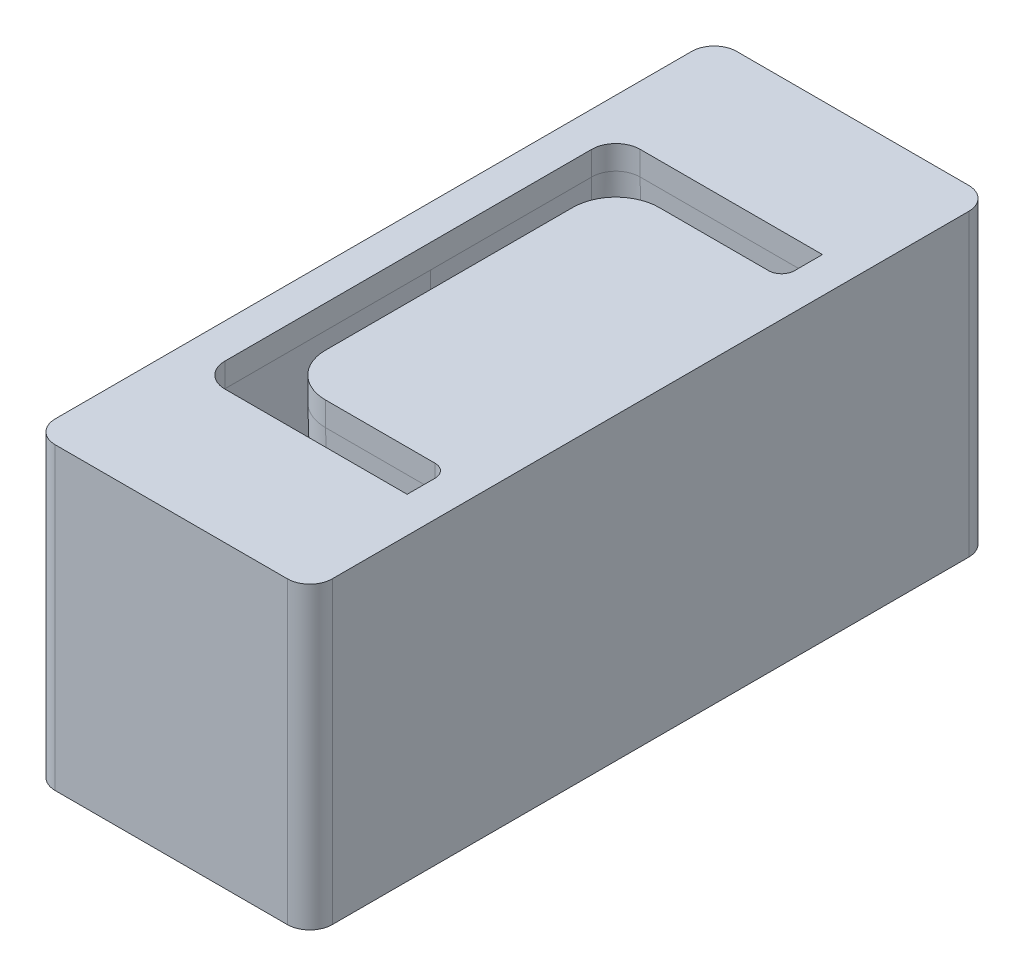
SolidWorks part; units mm, degrees
material "K110"
ref_plane "Front Plane" through (0, 0, 0) normal (0, 0, 1) x (1, 0, 0)
ref_plane "Top Plane" through (0, 0, 0) normal (0, 1, 0) x (1, 0, 0)
ref_plane "Right Plane" through (0, 0, 0) normal (1, 0, 0) x (0, 0, -1)
sketch "Sketch1" plane through (0, 0, 0) normal (0, 1, 0) x (1, 0, 0)
  line L1 (-8, -48.5) -> (29, -48.5)
  line L2 (-8, -48.5) -> (-8, 42.5)
  line L3 (-8, 42.5) -> (29, 42.5)
  line L4 (29, -48.5) -> (29, 42.5)
  line L5 (10.5, 42.5) -> (10.5, -48.5) construction
  line L6 (26, 42.5) -> (-5, 42.5) construction
  line L8 (-5, -48.5) -> (26, -48.5) construction
  line L9 (29, -3) -> (-8, -3) construction
  line L10 (29, -45.5) -> (29, 39.5) construction
  line L11 (-8, 39.5) -> (-8, -45.5) construction
  point P0 (0, 0)
extrude "Boss-Extrude1" add sketch "Sketch1" against normal blind 40
fillet "Fillet1" radius 3 4 edges at (-8, -20, -42.5) (29, -20, -42.5) (29, -20, 48.5) (-8, -20, 48.5)
sketch "Sketch2" plane through (0, 0, 0) normal (0, 1, 0) x (1, 0, 0)
  line L46 (24.23, 24.73) -> (-0.12, 24.73)
  line L47 (24.23, 21) -> (24.23, 24.73)
  line L48 (7.88, 19.27) -> (22.5, 19.27)
  line L49 (2.11, -19.5) -> (2.11, 13.5)
  line L60 (22.5, -25.27) -> (7.88, -25.27)
  line L61 (24.23, -30.73) -> (24.23, -27)
  line L62 (-0.12, -30.73) -> (24.23, -30.73)
  line L63 (-3.35, 21.5) -> (-3.35, -27.5)
  line L64 (24.23, 24.73) -> (-0.12, 24.73)
  line L65 (24.23, 21) -> (24.23, 24.73)
  line L66 (7.88, 19.27) -> (22.5, 19.27)
  line L67 (2.11, -19.5) -> (2.11, 13.5)
  line L68 (22.5, -25.27) -> (7.88, -25.27)
  line L69 (24.23, -30.73) -> (24.23, -27)
  line L70 (-0.12, -30.73) -> (24.23, -30.73)
  line L71 (-3.35, 21.5) -> (-3.35, -27.5)
  arc A36 (-0.12, 24.73) -> (-3.35, 21.5) centre (-0.12, 21.5) ccw
  arc A37 (22.5, 19.27) -> (24.23, 21) centre (22.5, 21) ccw
  arc A38 (7.88, 19.27) -> (2.11, 13.5) centre (7.88, 13.5) ccw
  arc A39 (2.11, -19.5) -> (7.88, -25.27) centre (7.88, -19.5) ccw
  arc A40 (24.23, -27) -> (22.5, -25.27) centre (22.5, -27) ccw
  arc A41 (-3.35, -27.5) -> (-0.12, -30.73) centre (-0.12, -27.5) ccw
  arc A42 (-0.12, 24.73) -> (-3.35, 21.5) centre (-0.12, 21.5) ccw
  arc A43 (22.5, 19.27) -> (24.23, 21) centre (22.5, 21) ccw
  arc A44 (7.88, 19.27) -> (2.11, 13.5) centre (7.88, 13.5) ccw
  arc A45 (2.11, -19.5) -> (7.88, -25.27) centre (7.88, -19.5) ccw
  arc A46 (24.23, -27) -> (22.5, -25.27) centre (22.5, -27) ccw
  arc A47 (-3.35, -27.5) -> (-0.12, -30.73) centre (-0.12, -27.5) ccw
  dimension "D1" = 0.23
extrude "Cut-Extrude1" cut sketch "Sketch2" against normal up to next
sketch "Sketch3" plane through (0, 0, 0) normal (0, 0, 1) x (1, 0, 0)
  line L0 (-3.35, -3.2) -> (-3.9923, -40)
  line L2 (-5, -40) -> (26, -40) construction
  line L3 (-3.9923, -40) -> (-3.35, -40)
  line L4 (-3.35, -40) -> (-3.35, -3.2)
  line L5 (20.35, 0) -> (-20.35, 0) construction
  line L7 (-3.35, -40) -> (-3.35, 0) construction
  point P2 (0, 0)
  point P10 (0, 0)
  point P12 (0, 0)
  dimension "D1" = 1
  dimension "D2" = 3.2
sketch "Sketch4" plane through (0, 0, 0) normal (0, 1, 0) x (1, 0, 0)
  line L16 (24.23, 21) -> (24.23, 24.73) construction
  line L17 (24.23, -30.73) -> (24.23, -27) construction
  line L18 (22.5, -25.27) -> (7.88, -25.27) construction
  line L19 (2.11, -19.5) -> (2.11, 13.5) construction
  line L20 (7.88, 19.27) -> (22.5, 19.27) construction
  line L21 (-0.12, -30.73) -> (24.23, -30.73) construction
  line L22 (-3.35, 21.5) -> (-3.35, -27.5) construction
  line L23 (24.23, 24.73) -> (-0.12, 24.73) construction
  line L24 (24.23, 21) -> (24.23, 24.73)
  line L25 (24.23, -30.73) -> (24.23, -27)
  line L26 (22.5, -25.27) -> (7.88, -25.27)
  line L27 (2.11, -19.5) -> (2.11, 13.5)
  line L28 (7.88, 19.27) -> (22.5, 19.27)
  line L29 (-0.12, -30.73) -> (24.23, -30.73)
  line L30 (-3.35, 21.5) -> (-3.35, -27.5)
  line L31 (24.23, 24.73) -> (-0.12, 24.73)
  arc A12 (22.5, 19.27) -> (24.23, 21) centre (22.5, 21) ccw construction
  arc A13 (24.23, -27) -> (22.5, -25.27) centre (22.5, -27) ccw construction
  arc A14 (2.11, -19.5) -> (7.88, -25.27) centre (7.88, -19.5) ccw construction
  arc A15 (7.88, 19.27) -> (2.11, 13.5) centre (7.88, 13.5) ccw construction
  arc A16 (-3.35, -27.5) -> (-0.12, -30.73) centre (-0.12, -27.5) ccw construction
  arc A17 (-0.12, 24.73) -> (-3.35, 21.5) centre (-0.12, 21.5) ccw construction
  arc A18 (22.5, 19.27) -> (24.23, 21) centre (22.5, 21) ccw
  arc A19 (24.23, -27) -> (22.5, -25.27) centre (22.5, -27) ccw
  arc A20 (2.11, -19.5) -> (7.88, -25.27) centre (7.88, -19.5) ccw
  arc A21 (7.88, 19.27) -> (2.11, 13.5) centre (7.88, 13.5) ccw
  arc A22 (-3.35, -27.5) -> (-0.12, -30.73) centre (-0.12, -27.5) ccw
  arc A23 (-0.12, 24.73) -> (-3.35, 21.5) centre (-0.12, 21.5) ccw
sweep "Cut-Sweep1" cut profiles "Sketch3" path "Sketch4"
hole_wizard "M8 Tapped Hole1" positions "Sketch7" profile "Sketch6" tap size "M8" standard "ISO"
sketch "Sketch7" plane through (0, -40, 0) normal (0, -1, 0) x (-1, 0, 0)
  line L0 (-10.5, 42.5) -> (-10.5, 25.3723) construction
  line L1 (-26, 42.5) -> (5, 42.5) construction
  line L4 (-10.5, -48.5) -> (-10.5, -31.3723) construction
  line L5 (5, -48.5) -> (-26, -48.5) construction
  line L8 (0.12, 25.3723) -> (-24.8723, 25.3723) construction
  line L9 (-24.8723, -31.3723) -> (0.12, -31.3723) construction
  point P0 (-10.5, 33.9362)
  point P2 (-10.5, -39.9362)
  point P21 (0, 0)
  point P22 (0, 0)
  point P23 (0, 0)
  point P26 (0, 0)
sketch "Sketch6" plane through (10.5, -40, -33.9362) normal (1, 0, 0) x (0, 0, -1)
  line L0 (0, 0) -> (0, 24.2929)
  line L1 (0, 24.2929) -> (3.4, 22.25)
  line L2 (3.4, 22.25) -> (3.4, 0)
  line L5 (3.4, 0) -> (0, 0)
  line L10 (0, 24.2929) -> (-3.4, 22.25) construction
  line L11 (0, -6.35) -> (0, 107.95) construction
  dimension "Tap Drill Dia." = 6.8
  dimension "Tap Drill Depth" = 22.25
  dimension "Drill Angle" = 118
cosmetic thread "Hole Thread1"
cosmetic thread "Hole Thread2"
